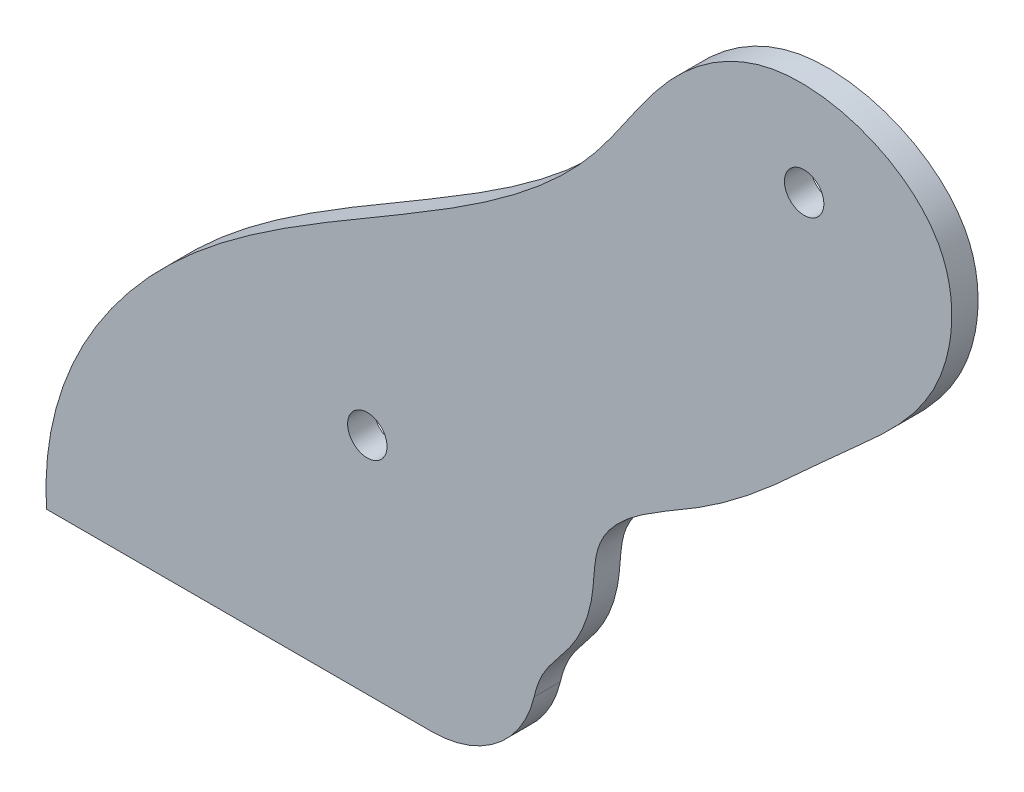
SolidWorks part; units mm, degrees
ref_plane "Front Plane" through (0, 0, 0) normal (0, 0, 1) x (1, 0, 0)
ref_plane "Top Plane" through (0, 0, 0) normal (0, 1, 0) x (1, 0, 0)
ref_plane "Right Plane" through (0, 0, 0) normal (1, 0, 0) x (0, 0, -1)
sketch "Sketch1" plane through (0, 0, 0) normal (0, 0, 1) x (1, 0, 0)
  line L0 (302.5, 350) -> (1512.5, 350) construction
  line L1 (417.5461, 18.659) -> (360.6441, 18.659)
  circle A0 centre (452.169, 97.5389) radius 2.3813
  circle A1 centre (399.4043, 45.7753) radius 2.3813
  spline S0 degree 3 poles (360.6441, 18.659) (359.8384, 32.3251) (373.1628, 53.4957) (402.4037, 70.0613) (425.1153, 83.9571) (435.1682, 102.1557) (450.4128, 112.1676) (471.3226, 103.8755) (469.7029, 83.4452) (454.9628, 71.5616) (442.6458, 58.7735) (426.7126, 51.6623) (426.837, 41.7869) (424.6062, 36.0701) (418.2307, 29.8094) (419.3141, 22.1393) (417.5461, 18.659) knots 0 0 0 0 0.153616 0.274149 0.398594 0.457962 0.516432 0.601433 0.654877 0.725582 0.814973 0.878082 0.897227 0.926553 0.948639 1 1 1 1
  dimension "D33" = 4.7625
  dimension "D34" = 4.7625
  dimension "D1" = 360.6441
  dimension "D2" = 364.558
  dimension "D3" = 376.9018
  dimension "D4" = 402.1916
  dimension "D5" = 417.5461
  dimension "D6" = 419.6536
  dimension "D7" = 420.5568
  dimension "D8" = 423.8685
  dimension "D9" = 426.5781
  dimension "D10" = 427.1803
  dimension "D11" = 436.2123
  dimension "D12" = 439.223
  dimension "D13" = 449.1583
  dimension "D14" = 456.685
  dimension "D15" = 468.4267
  dimension "D16" = 468.7277
  dimension "D17" = 18.659
  dimension "D18" = 28.8953
  dimension "D19" = 31.3038
  dimension "D20" = 35.8199
  dimension "D21" = 37.0241
  dimension "D22" = 42.7444
  dimension "D23" = 47.5615
  dimension "D24" = 52.9808
  dimension "D25" = 58.0989
  dimension "D26" = 70.1417
  dimension "D27" = 72.5502
  dimension "D28" = 86.0983
  dimension "D29" = 89.4101
  dimension "D30" = 99.6464
  dimension "D31" = 101.4528
  dimension "D32" = 108.6784
extrude "Boss-Extrude1" add sketch "Sketch1" along normal blind 3.175 contours S0 L1 | A1 | A0
fillet "Fillet1" radius 12.7 1 edges at (417.5461, 18.659, 1.5875)
